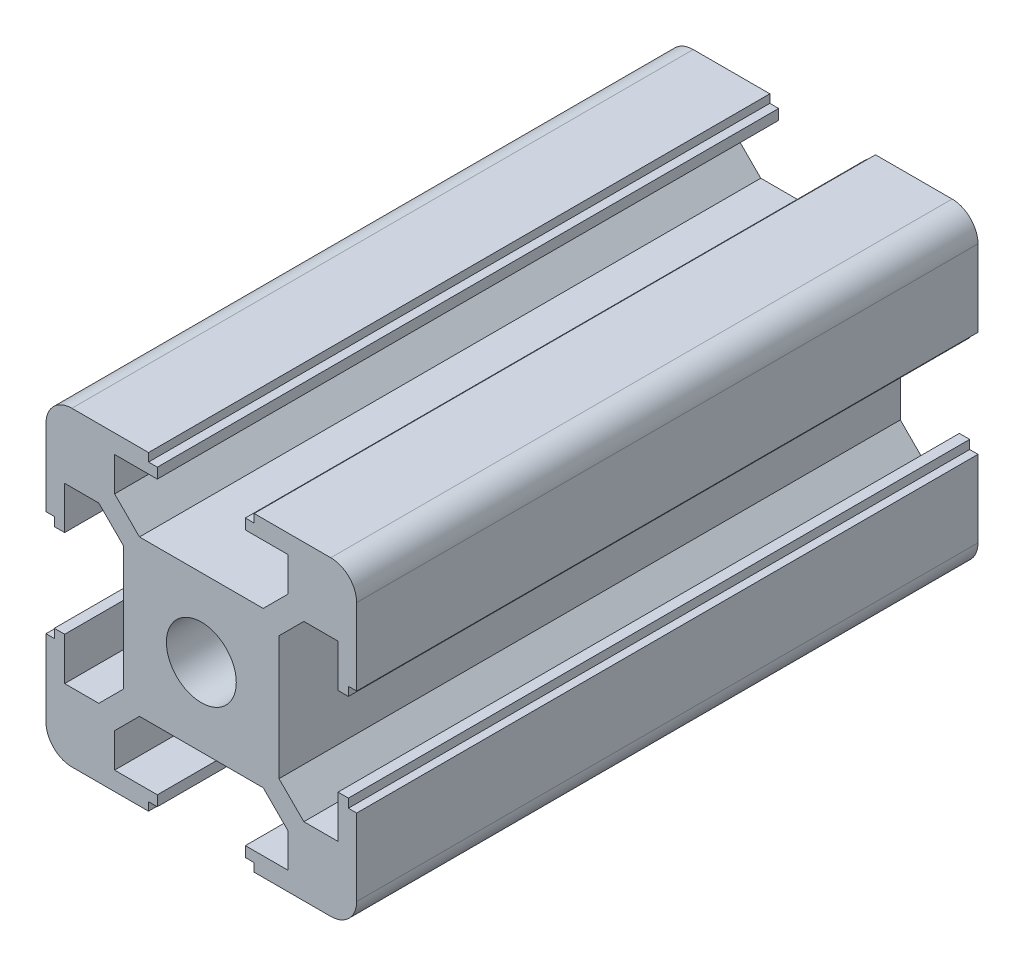
SolidWorks part; units mm, degrees
ref_plane "Front Plane" through (0, 0, 0) normal (0, 0, 1) x (1, 0, 0)
ref_plane "Top Plane" through (0, 0, 0) normal (0, 1, 0) x (1, 0, 0)
ref_plane "Right Plane" through (0, 0, 0) normal (1, 0, 0) x (0, 0, -1)
sketch "Sketch1" plane through (0, 0, 0) normal (0, 0, 1) x (1, 0, 0)
  line L1 (-15, -15) -> (15, -15)
  line L2 (-15, -15) -> (-15, 15)
  line L3 (-15, 15) -> (15, 15)
  line L4 (15, -15) -> (15, 15)
  line L5 (-15, -15) -> (15, 15) construction
  line L6 (-15, 15) -> (15, -15) construction
  point P0 (0, 0)
  dimension "D1" = 30
  dimension "D2" = 30
extrude "Boss-Extrude1" add sketch "Sketch1" along normal mid plane 60
sketch "Sketch2" plane through (0, 0, 30) normal (0, 0, 1) x (1, 0, 0)
  circle A0 centre (0, 0) radius 3.375
  dimension "D1" = 6.75
extrude "Cut-Extrude1" cut sketch "Sketch2" against normal through all
cosmetic thread "Cosmetic Thread1" parameters "D1"=12, "D2"=8
cosmetic thread "Cosmetic Thread2" parameters "D1"=12, "D2"=8
fillet "Fillet1" radius 2.5 4 edges at (15, -15, 0) (-15, -15, 0) (15, 15, 0) (-15, 15, 0)
sketch "Sketch3" plane through (0, 0, 30) normal (0, 0, 1) x (1, 0, 0)
  line L0 (0, -1000) -> (0, 49000) construction
  line L1 (0, 15) -> (-5.1, 15)
  line L2 (12.5, 15) -> (-12.5, 15) construction
  line L3 (-5.1, 15) -> (-5.1, 14.2)
  line L4 (-5.1, 14.2) -> (-4.25, 14.2)
  line L5 (-4.25, 14.2) -> (-4.25, 13.2)
  line L6 (-4.25, 13.2) -> (-8.375, 13.2)
  line L7 (-8.375, 13.2) -> (-8.375, 9.9)
  line L8 (-8.375, 9.9) -> (-5.975, 7.5)
  line L9 (-5.975, 7.5) -> (0, 7.5)
  line L10 (0, 7.5) -> (0, 15)
  dimension "D1" = 5.1
  dimension "D2" = 4.25
  dimension "D3" = 1.8
  dimension "D4" = 1
  dimension "D5" = 3.3
  dimension "D6" = 8.375
  dimension "D7" = 135
  dimension "D8" = 7.5
extrude "Cut-Extrude2" cut sketch "Sketch3" against normal through all
mirror "Mirror1" about plane through (0, 0, 0) normal (1, 0, 0) of "Cut-Extrude2"
pattern_circular "CirPattern1" count 4 over 360 about axis through (0, 0, -30) along (0, 0, 1) of "Mirror1"
